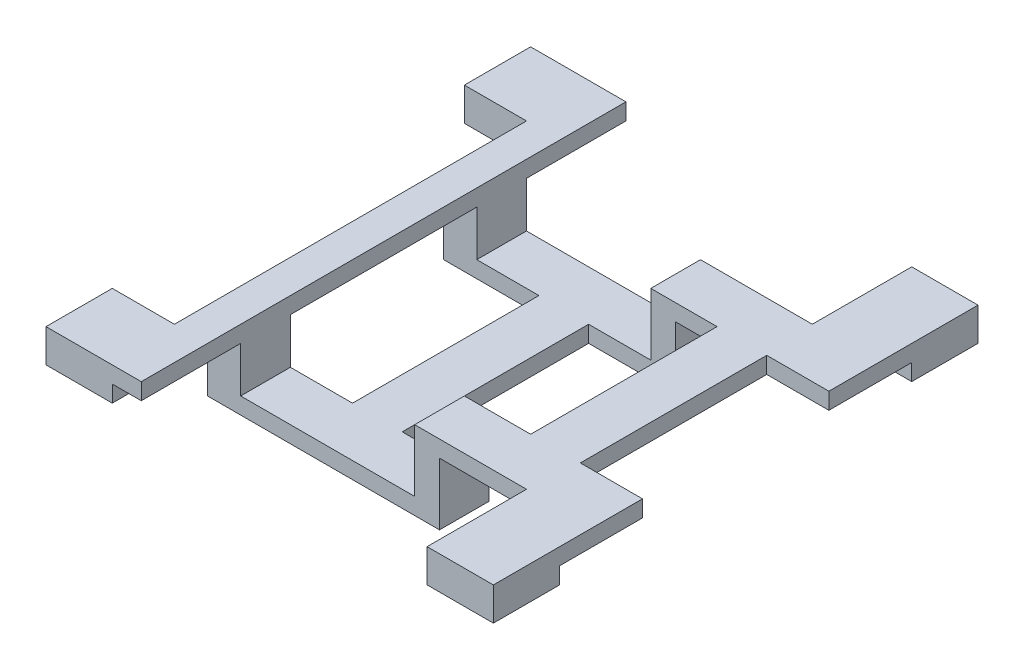
SolidWorks part; units mm, degrees
ref_plane "Front Plane" through (0, 0, 0) normal (0, 0, 1) x (1, 0, 0)
ref_plane "Top Plane" through (0, 0, 0) normal (0, 1, 0) x (1, 0, 0)
ref_plane "Right Plane" through (0, 0, 0) normal (1, 0, 0) x (0, 0, -1)
sketch "Sketch1" plane through (0, 0, 0) normal (0, 1, 0) x (1, 0, 0)
  line L1 (-56.5, 42.5) -> (56.5, 42.5)
  line L2 (-56.5, 42.5) -> (-56.5, -42.5)
  line L3 (-56.5, -42.5) -> (56.5, -42.5)
  line L4 (56.5, 42.5) -> (56.5, -42.5)
  line L5 (-56.5, 42.5) -> (56.5, -42.5) construction
  line L6 (-56.5, -42.5) -> (56.5, 42.5) construction
  point P0 (0, 0)
  dimension "D1" = 113
  dimension "D2" = 85
extrude "Boss-Extrude1" add sketch "Sketch1" along normal blind 4
sketch "Sketch4" plane through (0, 0, 0) normal (0, -1, 0) x (1, 0, 0)
  line L0 (-56.5, 42.5) -> (56.5, 42.5) construction
  line L5 (-56.5, 42.5) -> (-40.5, 42.5)
  line L6 (-56.5, 42.5) -> (-56.5, 58.5)
  line L7 (-56.5, 58.5) -> (-40.5, 58.5)
  line L8 (-40.5, 42.5) -> (-40.5, 58.5)
  line L9 (51.5, 42.5) -> (35.5, 42.5)
  line L10 (51.5, 42.5) -> (51.5, 58.5)
  line L11 (51.5, 58.5) -> (35.5, 58.5)
  line L12 (35.5, 42.5) -> (35.5, 58.5)
  line L18 (56.5, 42.5) -> (56.5, -42.5) construction
  line L19 (0, 0) -> (-56.5, 0) construction
  line L20 (-56.5, -42.5) -> (-56.5, 42.5) construction
  line L21 (51.5, -58.5) -> (35.5, -58.5)
  line L22 (35.5, -42.5) -> (35.5, -58.5)
  line L23 (51.5, -42.5) -> (35.5, -42.5)
  line L24 (51.5, -42.5) -> (51.5, -58.5)
  line L25 (-56.5, -58.5) -> (-40.5, -58.5)
  line L26 (-40.5, -42.5) -> (-40.5, -58.5)
  line L27 (-56.5, -42.5) -> (-40.5, -42.5)
  line L28 (-56.5, -42.5) -> (-56.5, -58.5)
  dimension "D1" = 16
  dimension "D2" = 16
  dimension "D3" = 5
  dimension "D4" = 16
  dimension "D5" = 16
extrude "Boss-Extrude3" add sketch "Sketch4" against normal up to surface (4 mm away) and the other way blind 1 up to face at (0, 4, 0)
sketch "Sketch10" plane through (0, 4, 0) normal (0, 1, 0) x (1, 0, 0)
  line L0 (-40.5, -58.5) -> (-56.5, -58.5) construction
  line L1 (-40.5, -42.5) -> (-30.5, -42.5)
  line L2 (-40.5, -42.5) -> (-40.5, -58.5)
  line L3 (-40.5, -58.5) -> (-30.5, -58.5)
  line L4 (-30.5, -42.5) -> (-30.5, -58.5)
  line L5 (-40.5, 42.5) -> (-30.5, 42.5)
  line L6 (-40.5, 42.5) -> (-40.5, 58.5)
  line L7 (-40.5, 58.5) -> (-30.5, 58.5)
  line L8 (-30.5, 42.5) -> (-30.5, 58.5)
  line L9 (-56.5, 58.5) -> (-40.5, 58.5) construction
  dimension "D1" = 10
  dimension "D2" = 10
extrude "Boss-Extrude6" add sketch "Sketch10" against normal up to surface (4 mm away) up to face at (9.3, 0, 0)
sketch "Sketch6" plane through (0, 4, 0) normal (0, 1, 0) x (1, 0, 0)
  line L0 (35.5, 42.5) -> (35.5, 58.5) construction
  line L1 (-31.5, 22.5) -> (41.5, 22.5)
  line L2 (-31.5, 22.5) -> (-31.5, -22.5)
  line L3 (-31.5, -22.5) -> (41.5, -22.5)
  line L4 (41.5, 22.5) -> (41.5, -22.5)
  line L5 (35.5, -58.5) -> (35.5, -42.5) construction
  line L6 (35.5, 42.5) -> (-30.5, 42.5) construction
  line L7 (-30.5, -42.5) -> (35.5, -42.5) construction
  line L8 (-56.5, 58.5) -> (-56.5, -58.5) construction
  line L9 (-41.5, 0) -> (-56.5, 0) construction
  line L10 (-56.5, 42.5) -> (-41.5, 42.5)
  line L11 (-56.5, 42.5) -> (-56.5, -42.5)
  line L12 (-56.5, -42.5) -> (-41.5, -42.5)
  line L13 (-41.5, 42.5) -> (-41.5, -42.5)
  line L14 (-31.5, 0) -> (41.5, 0) construction
  line L15 (-30.5, 42.5) -> (35.5, 42.5)
  line L16 (-30.5, 42.5) -> (-30.5, 34.5)
  line L17 (-30.5, 34.5) -> (35.5, 34.5)
  line L18 (35.5, 42.5) -> (35.5, 34.5)
  line L19 (-30.5, -42.5) -> (35.5, -42.5)
  line L20 (-30.5, -42.5) -> (-30.5, -34.5)
  line L21 (-30.5, -34.5) -> (35.5, -34.5)
  line L22 (35.5, -42.5) -> (35.5, -34.5)
  line L23 (56.5, -42.5) -> (56.5, 42.5) construction
  dimension "D1" = 20
  dimension "D2" = 20
  dimension "D3" = 25
  dimension "D4" = 15
  dimension "D5" = 85
  dimension "D6" = 8
  dimension "D7" = 8
  dimension "D8" = 15
extrude "Cut-Extrude2" cut sketch "Sketch6" against normal through all
sketch "Sketch8" plane through (0, -1, 0) normal (0, -1, 0) x (1, 0, 0)
  line L0 (-56.5, 58.5) -> (-40.5, 58.5) construction
  line L1 (-56.5, 58.5) -> (-56.5, 42.5) construction
  line L2 (-56.5, 42.5) -> (-40.5, 42.5) construction
  line L3 (-40.5, 58.5) -> (-40.5, 42.5) construction
  line L4 (35.5, 58.5) -> (51.5, 58.5) construction
  line L5 (35.5, 58.5) -> (35.5, 42.5) construction
  line L6 (35.5, 42.5) -> (51.5, 42.5) construction
  line L7 (51.5, 58.5) -> (51.5, 42.5) construction
  line L8 (-56.5, 58.5) -> (-40.5, 42.5) construction
  line L9 (-56.5, 42.5) -> (-40.5, 58.5) construction
  line L10 (35.5, 58.5) -> (51.5, 42.5) construction
  line L11 (35.5, 42.5) -> (51.5, 58.5) construction
  line L12 (51.5, 58.5) -> (35.5, 58.5) construction
  line L13 (0, 0) -> (-56.5, 0) construction
  line L14 (-56.5, 42.5) -> (-40.5, 42.5) construction
  line L15 (35.5, 42.5) -> (51.5, 42.5) construction
  circle A0 centre (-48.5, 50.5) radius 6.1
  circle A1 centre (43.5, 50.5) radius 6.1
  circle A2 centre (43.5, -50.5) radius 6.1
  circle A3 centre (-48.5, -50.5) radius 6.1
  dimension "D3" = 12.2
  dimension "D4" = 12.2
extrude "Cut-Extrude3" cut sketch "Sketch8" against normal blind 3.2
sketch "Sketch9" plane through (0, -1, 0) normal (0, -1, 0) x (1, 0, 0)
  line L0 (-55.5, 57.5) -> (-55.5, 43.5)
  line L1 (-56.5, 58.5) -> (-40.5, 58.5)
  line L2 (-56.5, 58.5) -> (-56.5, 42.5)
  line L3 (-56.5, 42.5) -> (-40.5, 42.5)
  line L4 (-40.5, 58.5) -> (-40.5, 42.5)
  line L5 (35.5, 58.5) -> (51.5, 58.5)
  line L6 (35.5, 58.5) -> (35.5, 42.5)
  line L7 (35.5, 42.5) -> (51.5, 42.5)
  line L8 (51.5, 58.5) -> (51.5, 42.5)
  line L9 (-55.5, 43.5) -> (-41.5, 43.5)
  line L10 (-41.5, 57.5) -> (-41.5, 43.5)
  line L11 (-55.5, 57.5) -> (-41.5, 57.5)
  line L16 (0, 0) -> (-56.5, 0) construction
  line L17 (36.5, -43.5) -> (50.5, -43.5)
  line L18 (36.5, -57.5) -> (36.5, -43.5)
  line L19 (50.5, -57.5) -> (36.5, -57.5)
  line L20 (50.5, 43.5) -> (50.5, 57.5)
  line L21 (50.5, 57.5) -> (36.5, 57.5)
  line L22 (36.5, 57.5) -> (36.5, 43.5)
  line L23 (36.5, 43.5) -> (50.5, 43.5)
  line L24 (50.5, 43.5) -> (50.5, 57.5)
  line L25 (50.5, 57.5) -> (36.5, 57.5)
  line L26 (36.5, 57.5) -> (36.5, 43.5)
  line L27 (36.5, 43.5) -> (50.5, 43.5)
  line L28 (50.5, -43.5) -> (50.5, -57.5)
  line L29 (-55.5, -57.5) -> (-41.5, -57.5)
  line L30 (-41.5, -57.5) -> (-41.5, -43.5)
  line L31 (-55.5, -43.5) -> (-41.5, -43.5)
  line L32 (51.5, -58.5) -> (51.5, -42.5)
  line L33 (35.5, -42.5) -> (51.5, -42.5)
  line L34 (35.5, -58.5) -> (35.5, -42.5)
  line L35 (35.5, -58.5) -> (51.5, -58.5)
  line L36 (-40.5, -58.5) -> (-40.5, -42.5)
  line L37 (-56.5, -42.5) -> (-40.5, -42.5)
  line L38 (-56.5, -58.5) -> (-56.5, -42.5)
  line L39 (-56.5, -58.5) -> (-40.5, -58.5)
  line L40 (-55.5, -57.5) -> (-55.5, -43.5)
  dimension "D1" = 1
  dimension "D2" = 1
extrude "Boss-Extrude5" add sketch "Sketch9" along normal blind 3
fillet "Fillet1" radius 0.2 4 edges at (43.5, -1, -44.4) (-48.5, -1, -44.4) (43.5, -1, 44.4) (-48.5, -1, 44.4)
sketch "Sketch13" plane through (56.5, 0, 0) normal (1, 0, 0) x (0, 0, -1)
  line L1 (-42.5, 4) -> (42.5, 4)
  line L2 (-42.5, 4) -> (-42.5, 0)
  line L3 (-42.5, 0) -> (42.5, 0)
  line L4 (42.5, 4) -> (42.5, 0)
extrude "Cut-Extrude4" cut sketch "Sketch13" against normal up to surface (5 mm away) up to face at (51.5, 0, 48.9)
sketch "Sketch14" plane through (0, 4, 0) normal (0, 1, 0) x (1, 0, 0)
  line L0 (-41.5, -42.5) -> (-41.5, 42.5) construction
  line L1 (-41.5, 22.5) -> (51.5, 22.5)
  line L2 (-41.5, 22.5) -> (-41.5, -22.5)
  line L3 (-41.5, -22.5) -> (51.5, -22.5)
  line L4 (51.5, 22.5) -> (51.5, -22.5)
  line L5 (51.5, 58.5) -> (51.5, -58.5) construction
  line L6 (-31.5, -22.5) -> (41.5, -22.5) construction
  line L7 (41.5, 22.5) -> (-31.5, 22.5) construction
extrude "Cut-Extrude5" cut sketch "Sketch14" against normal through all
sketch "Sketch15" plane through (0, 4, 0) normal (0, 1, 0) x (1, 0, 0)
  line L0 (51.5, 22.5) -> (-41.5, 22.5) construction
  line L1 (-18.5, 22.5) -> (-6.5, 22.5)
  line L2 (-18.5, 22.5) -> (-18.5, -22.5)
  line L3 (-18.5, -22.5) -> (-6.5, -22.5)
  line L4 (-6.5, 22.5) -> (-6.5, -22.5)
  line L5 (-41.5, -22.5) -> (51.5, -22.5) construction
  line L6 (51.5, -22.5) -> (51.5, -58.5) construction
  line L7 (24.5, 22.5) -> (36.5, 22.5)
  line L8 (24.5, 22.5) -> (24.5, -22.5)
  line L9 (24.5, -22.5) -> (36.5, -22.5)
  line L10 (36.5, 22.5) -> (36.5, -22.5)
  line L11 (-41.5, -42.5) -> (-41.5, -22.5) construction
  dimension "D1" = 12
  dimension "D2" = 12
  dimension "D3" = 15
  dimension "D4" = 23
extrude "Boss-Extrude7" add sketch "Sketch15" against normal up to surface (4 mm away) up to face at (-5.1, 0, 40.1)
sketch "Sketch16" plane through (0, 0, 0) normal (0, -1, 0) x (1, 0, 0)
  line L24 (24.5, 22.5) -> (24.5, -22.5) construction
  line L25 (24.5, -22.5) -> (-6.5, -22.5) construction
  line L26 (-6.5, -22.5) -> (-6.5, 22.5) construction
  line L27 (-6.5, 22.5) -> (24.5, 22.5) construction
  line L28 (24.5, 22.5) -> (24.5, -22.5) construction
  line L29 (24.5, -22.5) -> (-6.5, -22.5) construction
  line L30 (-6.5, -22.5) -> (-6.5, 22.5)
  line L31 (-6.5, 22.5) -> (24.5, 22.5) construction
  line L36 (-30.5, -34.5) -> (14.5, -34.5)
  line L37 (14.5, -34.5) -> (14.5, -22.5)
  line L38 (14.5, -22.5) -> (-6.5, -22.5)
  line L39 (-6.5, 22.5) -> (14.5, 22.5)
  line L40 (14.5, 22.5) -> (14.5, 34.5)
  line L41 (14.5, 34.5) -> (-30.5, 34.5)
  line L42 (-18.5, 22.5) -> (-41.5, 22.5)
  line L43 (-41.5, 22.5) -> (-18.5, 22.5) construction
  line L44 (-41.5, 22.5) -> (-41.5, 34.5)
  line L45 (-41.5, 34.5) -> (-30.5, 34.5)
  line L46 (-18.5, -22.5) -> (-41.5, -22.5)
  line L47 (-18.5, -22.5) -> (-41.5, -22.5) construction
  line L48 (-41.5, 42.5) -> (-41.5, 22.5)
  line L49 (-41.5, 22.5) -> (-18.5, 22.5)
  line L50 (-18.5, 22.5) -> (-18.5, -22.5)
  line L51 (-18.5, -22.5) -> (-41.5, -22.5)
  line L52 (-41.5, -22.5) -> (-41.5, -42.5)
  line L53 (-41.5, -42.5) -> (-40.5, -42.5)
  line L54 (-40.5, -42.5) -> (-40.5, -58.5)
  line L55 (-40.5, -58.5) -> (-30.5, -58.5)
  line L56 (-30.5, -58.5) -> (-30.5, -34.5)
  line L57 (-30.5, -34.5) -> (35.5, -34.5)
  line L58 (35.5, -34.5) -> (35.5, -42.5)
  line L59 (35.5, -42.5) -> (51.5, -42.5)
  line L60 (51.5, -42.5) -> (51.5, -22.5)
  line L61 (51.5, -22.5) -> (36.5, -22.5)
  line L62 (36.5, -22.5) -> (36.5, 22.5)
  line L63 (36.5, 22.5) -> (51.5, 22.5)
  line L64 (51.5, 22.5) -> (51.5, 42.5)
  line L65 (51.5, 42.5) -> (35.5, 42.5)
  line L66 (35.5, 42.5) -> (35.5, 34.5)
  line L67 (35.5, 34.5) -> (-30.5, 34.5)
  line L68 (-30.5, 34.5) -> (-30.5, 58.5)
  line L69 (-30.5, 58.5) -> (-40.5, 58.5)
  line L70 (-40.5, 58.5) -> (-40.5, 42.5)
  line L71 (-40.5, 42.5) -> (-41.5, 42.5)
  line L72 (-41.5, 42.5) -> (-41.5, 22.5) construction
  line L74 (-18.5, 22.5) -> (-18.5, -22.5)
  line L76 (-41.5, -22.5) -> (-41.5, -42.5) construction
  line L77 (-41.5, -42.5) -> (-40.5, -42.5) construction
  line L78 (-40.5, -42.5) -> (-40.5, -58.5) construction
  line L79 (-40.5, -58.5) -> (-30.5, -58.5) construction
  line L80 (-30.5, -58.5) -> (-30.5, -34.5) construction
  line L81 (-30.5, -34.5) -> (35.5, -34.5) construction
  line L82 (35.5, -34.5) -> (35.5, -42.5) construction
  line L83 (35.5, -42.5) -> (51.5, -42.5) construction
  line L84 (51.5, -42.5) -> (51.5, -22.5) construction
  line L85 (51.5, -22.5) -> (36.5, -22.5) construction
  line L86 (36.5, -22.5) -> (36.5, 22.5) construction
  line L87 (36.5, 22.5) -> (51.5, 22.5) construction
  line L88 (51.5, 22.5) -> (51.5, 42.5) construction
  line L89 (51.5, 42.5) -> (35.5, 42.5) construction
  line L90 (35.5, 42.5) -> (35.5, 34.5) construction
  line L91 (35.5, 34.5) -> (-30.5, 34.5) construction
  line L92 (-30.5, 34.5) -> (-30.5, 58.5) construction
  line L93 (-30.5, 58.5) -> (-40.5, 58.5) construction
  line L94 (-40.5, 58.5) -> (-40.5, 42.5) construction
  line L95 (-40.5, 42.5) -> (-41.5, 42.5) construction
  line L96 (-41.5, -22.5) -> (-41.5, -34.5)
  line L97 (-41.5, -34.5) -> (-30.5, -34.5)
  dimension "D2" = 45
  dimension "D1" = 0
extrude "Boss-Extrude8" add sketch "Sketch16" along normal blind 15
sketch "Sketch17" plane through (0, 4, 0) normal (0, 1, 0) x (1, 0, 0)
  line L0 (-30.5, -58.5) -> (-56.5, -58.5) construction
  line L1 (-33.5, 58.5) -> (8.5, 58.5)
  line L2 (-33.5, 58.5) -> (-33.5, -58.5)
  line L3 (-33.5, -58.5) -> (8.5, -58.5)
  line L4 (8.5, 58.5) -> (8.5, -58.5)
  line L7 (-41.5, 22.5) -> (-41.5, 42.5) construction
  line L8 (-56.5, 58.5) -> (-30.5, 58.5) construction
  dimension "D1" = 8
  dimension "D2" = 42
extrude "Cut-Extrude6" cut sketch "Sketch17" against normal blind 15
sketch "Sketch18" plane through (0, 4, 0) normal (0, 1, 0) x (1, 0, 0)
  line L1 (-33.5, 22.5) -> (-41.5, 22.5)
  line L2 (-33.5, 22.5) -> (-33.5, -22.5)
  line L3 (-33.5, -22.5) -> (-41.5, -22.5)
  line L4 (-41.5, 22.5) -> (-41.5, -22.5)
extrude "Boss-Extrude9" add sketch "Sketch18" against normal blind 4
